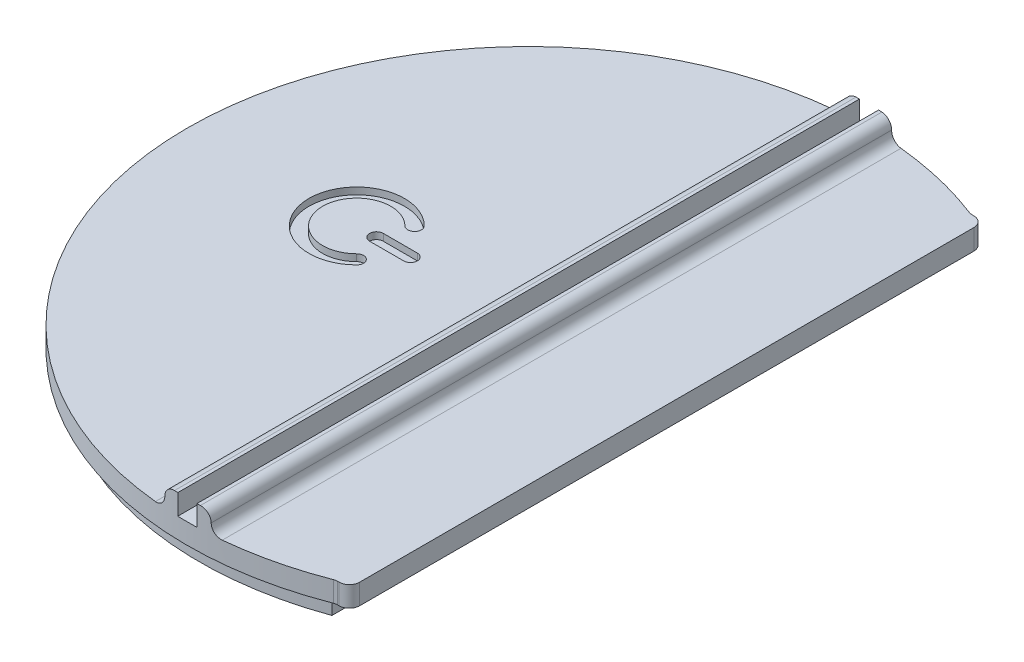
SolidWorks part; units mm, degrees
ref_plane "Front Plane" through (0, 0, 0) normal (0, 0, 1) x (1, 0, 0)
ref_plane "Top Plane" through (0, 0, 0) normal (0, 1, 0) x (1, 0, 0)
ref_plane "Right Plane" through (0, 0, 0) normal (1, 0, 0) x (0, 0, -1)
sketch "Sketch1" plane through (0, 0, 0) normal (0, 1, 0) x (1, 0, 0)
  line L0 (18.31, 46.5268) -> (18.31, -46.5268)
  arc A0 (18.31, 46.5268) -> (18.31, -46.5268) centre (0, 0) ccw
  dimension "D1" = 100
  dimension "D2" = 18.31
extrude "Boss-Extrude1" add sketch "Sketch1" along normal blind 3
sketch "Sketch2" plane through (0, 3, 0) normal (0, 1, 0) x (1, 0, 0)
  line L1 (-1.4, 25) -> (1.4, 25)
  line L2 (-1.4, 25) -> (-1.4, -25)
  line L3 (-1.4, -25) -> (1.4, -25)
  line L4 (1.4, 25) -> (1.4, -25)
  line L5 (-1.4, 25) -> (1.4, -25) construction
  line L6 (-1.4, -25) -> (1.4, 25) construction
  point P0 (0, 0)
  dimension "D1" = 2.8
  dimension "D2" = 50
extrude "Cut-Extrude1" cut sketch "Sketch2" against normal through all both
sketch "Sketch3" plane through (0, 0, 0) normal (0, -1, 0) x (1, 0, 0)
  line L2 (16.51, -45.2842) -> (16.51, 45.2842)
  line L3 (16.51, -45.2842) -> (16.51, 45.2842)
  line L5 (14.51, -43.8623) -> (14.51, 43.8623)
  line L6 (14.51, -43.8623) -> (14.51, 43.8623)
  arc A2 (16.51, 45.2842) -> (16.51, -45.2842) centre (0, 0) ccw
  arc A3 (16.51, 45.2842) -> (16.51, -45.2842) centre (0, 0) ccw
  arc A6 (14.51, 43.8623) -> (14.51, -43.8623) centre (0, 0) ccw
  arc A7 (14.51, 43.8623) -> (14.51, -43.8623) centre (0, 0) ccw
  dimension "D1" = 1.8
  dimension "D2" = 3.8
extrude "Boss-Extrude2" add sketch "Sketch3" along normal blind 3
sketch "Sketch4" plane through (0, -3, 0) normal (0, -1, 0) x (1, 0, 0)
  line L0 (14.51, -43.8623) -> (14.51, 43.8623) construction
  line L1 (14.51, 8.4732) -> (16.51, 8.4732)
  line L2 (14.51, 8.4732) -> (14.51, -16.5268)
  line L3 (14.51, -16.5268) -> (16.51, -16.5268)
  line L4 (16.51, 8.4732) -> (16.51, -16.5268)
  line L5 (16.51, -45.2842) -> (16.51, 45.2842) construction
  dimension "D1" = 30
  dimension "D2" = 25
extrude "Cut-Extrude2" cut sketch "Sketch4" against normal up to surface (3 mm away) up to face at (-15.845, 0, 0)
sketch "Sketch6" plane through (0, 3, 0) normal (0, 1, 0) x (1, 0, 0)
  line L0 (-1.4, 49.9804) -> (-1.4, -49.9804)
  line L1 (-3.4, 49.8843) -> (-3.4, -49.8843)
  line L2 (1.4, 49.9804) -> (1.4, -49.9804)
  line L3 (3.4, 49.8843) -> (3.4, -49.8843)
  arc A0 (18.31, 46.5268) -> (18.31, -46.5268) centre (0, 0) ccw construction
  circle A1 centre (0, 0) radius 50
  line M4 (1.4, 25) -> (1.4, -25)
  line M6 (-1.4, -25) -> (-1.4, 25)
  arc M8 (18.31, 46.5268) -> (18.31, -46.5268) centre (0, 0) ccw
  dimension "D1" = 2
  dimension "D2" = 2
extrude "Boss-Extrude3" add sketch "Sketch6" along normal blind 3 contours L1 L0 M8 M6 | L3 L2 M8 M4 region at (-2.3997, 3, 0) region at (2.3997, 3, 0)
sketch "Sketch7" plane through (18.31, 0, 0) normal (1, 0, 0) x (0, 0, -1)
  line L1 (-46.5268, 3) -> (46.5268, 3)
  line L2 (-46.5268, 3) -> (-46.5268, 0)
  line L3 (-46.5268, 0) -> (46.5268, 0)
  line L4 (46.5268, 3) -> (46.5268, 0)
extrude "Boss-Extrude4" add sketch "Sketch7" along normal blind 2
sketch "Sketch8" plane through (0, 3, 0) normal (0, 1, 0) x (1, 0, 0)
  line L0 (-20.898, 4.2426) -> (-25.1407, 0) construction
  line L1 (-25.1407, 0) -> (-25.1407, 9.6998) construction
  line L2 (-17.2532, 1) -> (-22.2532, 1)
  line L3 (-17.2532, -1) -> (-22.2532, -1)
  arc A0 (-20.1909, 4.9497) -> (-20.1909, -4.9497) centre (-25.1407, 0) ccw
  arc A1 (-21.6051, 3.5355) -> (-21.6051, -3.5355) centre (-25.1407, 0) ccw
  arc A4 (-21.6051, 3.5355) -> (-20.1909, 4.9497) centre (-20.898, 4.2426) ccw
  arc A5 (-20.1909, -4.9497) -> (-21.6051, -3.5355) centre (-20.898, -4.2426) ccw
  arc A6 (-17.2532, -1) -> (-17.2532, 1) centre (-17.2532, 0) ccw
  arc A7 (-22.2532, 1) -> (-22.2532, -1) centre (-22.2532, 0) ccw
  point P1 (-16.349, 14.2585)
  point P4 (0, 0)
  point P7 (0, 0)
  dimension "D1" = 10
  dimension "D2" = 14
  dimension "D3" = 45
  dimension "D4" = 5
extrude "Cut-Extrude3" cut sketch "Sketch8" against normal blind 1
fillet "Fillet1" radius 1.5 8 edges at (20.31, 1.5, -46.5268) (18.31, 1.5, -46.5268) (20.31, 1.5, 46.5268) (18.31, 1.5, 46.5268) (-3.4, 6, 0) (3.4, 6, 0) (3.4, 3, 0) (-3.4, 3, 0)
